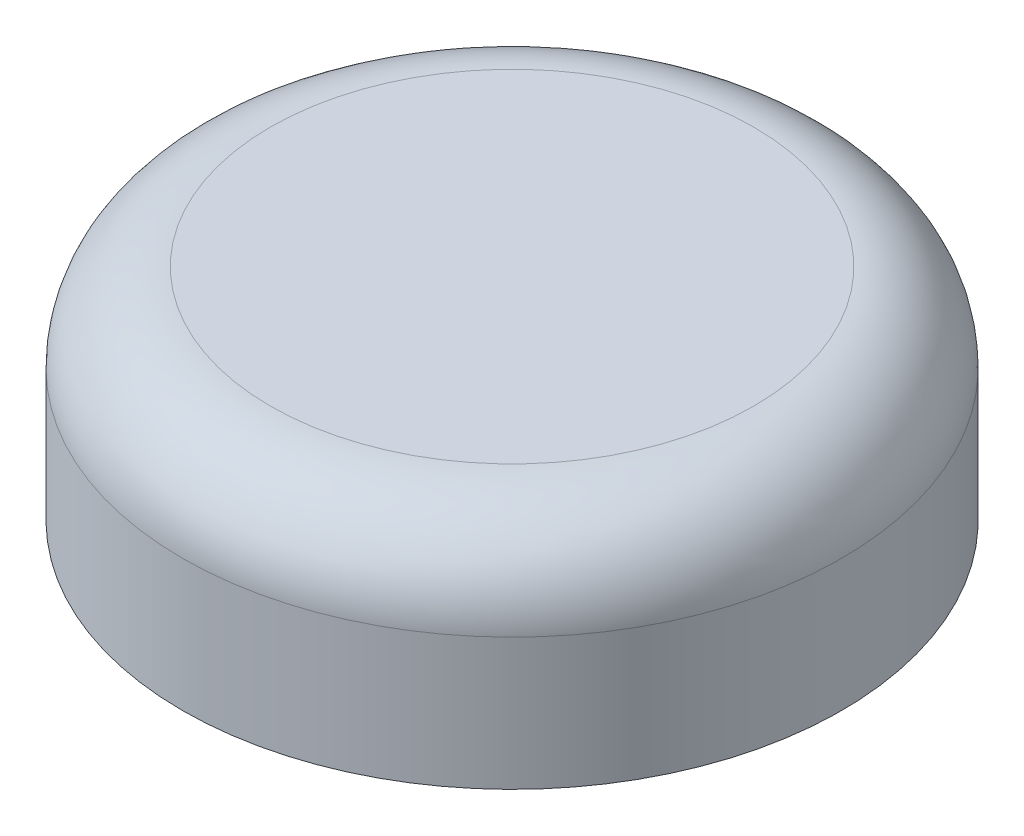
SolidWorks part; units mm, degrees
material "Delrin 2700 NC010, Low Viscosity Acetal Copolymer (SS)"
ref_plane "Front Plane" through (0, 0, 0) normal (0, 0, 1) x (1, 0, 0)
ref_plane "Top Plane" through (0, 0, 0) normal (0, 1, 0) x (1, 0, 0)
ref_plane "Right Plane" through (0, 0, 0) normal (1, 0, 0) x (0, 0, -1)
sketch "Sketch1" plane through (0, 0, 0) normal (0, 1, 0) x (1, 0, 0)
  circle A0 centre (0, 0) radius 9.525
  dimension "D1" = 19.05
extrude "Boss-Extrude1" add sketch "Sketch1" along normal blind 6.35
sketch "Sketch2" plane through (0, 0, 0) normal (0, -1, 0) x (1, 0, 0)
  circle A0 centre (0, 0) radius 3.175
  dimension "D1" = 6.35
extrude "Cut-Extrude1" cut sketch "Sketch2" against normal blind 3.175
fillet "Fillet1" radius 2.54 1 edges at (0, 6.35, 9.525)
